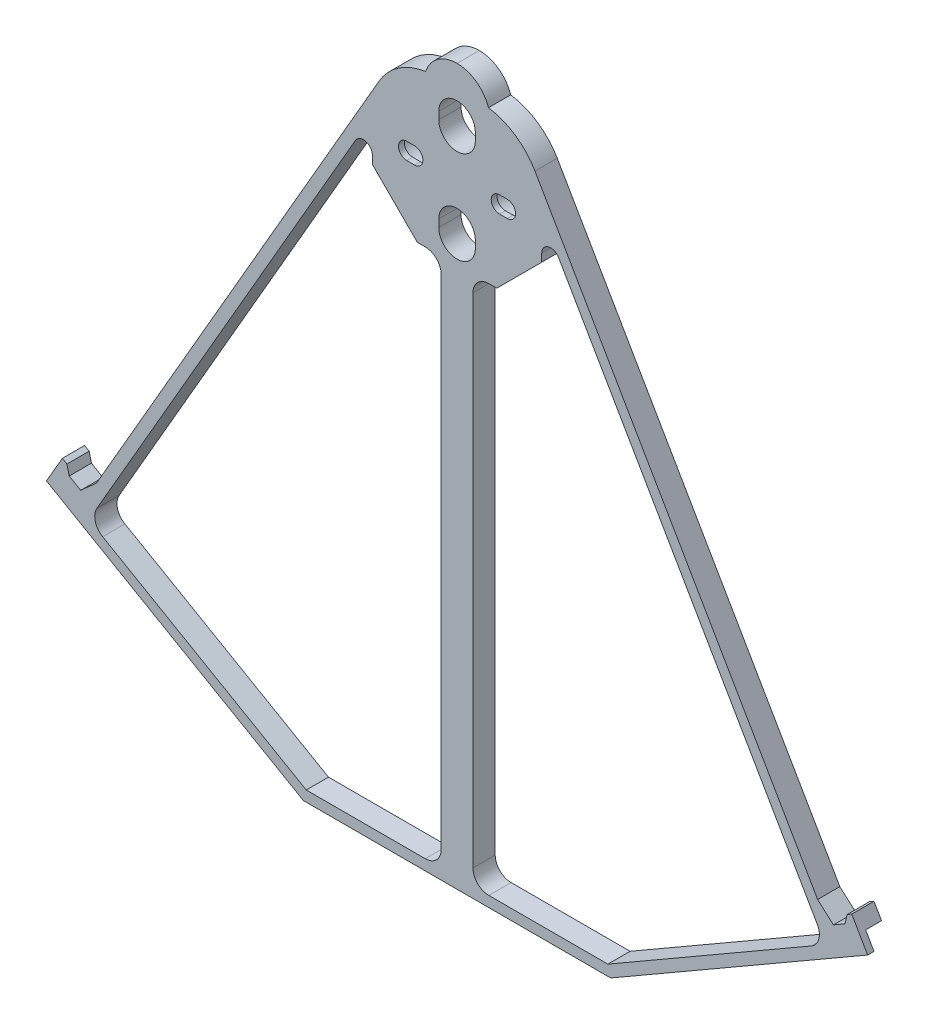
SolidWorks part; units mm, degrees
ref_plane "Alzado" through (0, 0, 0) normal (0, 0, 1) x (1, 0, 0)
ref_plane "Planta" through (0, 0, 0) normal (0, 1, 0) x (1, 0, 0)
ref_plane "Vista lateral" through (0, 0, 0) normal (1, 0, 0) x (0, 0, -1)
sketch "Croquis1" plane through (0, 0, 0) normal (0, 0, 1) x (1, 0, 0)
  line L0 (0, 0) -> (-29, 0)
  line L1 (0, 0) -> (0, 135)
  line L2 (-29, 0) -> (-77.4974, 28)
  line L3 (-77.4974, 28) -> (-74.4974, 33.1962)
  line L4 (-74.4974, 33.1962) -> (-73.6314, 32.6962)
  line L5 (-73.6314, 32.6962) -> (-74.2814, 31.5703)
  line L6 (-74.2814, 31.5703) -> (-69.9513, 29.0703)
  line L7 (-69.9513, 29.0703) -> (-8.7938, 134.9982)
  line L8 (-71.0381, 29.6978) -> (-68.0523, 32.3595)
  line L9 (-73.6314, 32.6962) -> (-73.2032, 30.9478)
  line L10 (0, 135) -> (-8.7938, 134.9982)
  point P4 (0, 0)
  dimension "D1" = 56
  dimension "D2" = 135
  dimension "D3" = 29
  dimension "D4" = 150
  dimension "D5" = 6
  dimension "D6" = 1
  dimension "D7" = 90
  dimension "D8" = 1.3
  dimension "D9" = 6
  dimension "D11" = 4
  dimension "D12" = 1.8
  dimension "D13" = 2.5
extrude "Saliente-Extruir1" add sketch "Croquis1" along normal blind 4.2 contours L1 L10 L7 L6 L5 L4 L3 L2 L0 | L8 L6 L7 | L9 L5 L6 region at (-25.21, 54.1538, 0) region at (-69.6806, 30.3759, 0) region at (-73.7053, 31.7381, 0)
sketch "Croquis2" plane through (0, 0, 4.2) normal (0, 0, 1) x (1, 0, 0)
  line L0 (0, 2) -> (-32.4641, 2)
  line L1 (0, 0) -> (0, 135) construction
  line L2 (-29, 0) -> (-77.4974, 28) construction
  line L3 (0, 0) -> (-29, 0) construction
  line L4 (-76.4974, 29.7321) -> (-28.4641, 2)
  line L5 (-68.0523, 32.3595) -> (-8.7938, 134.9982) construction
  line L6 (-70.4826, 23.95) -> (-6.3686, 134.9987)
  line L8 (-3, 2) -> (-3, 134.9994)
  line L10 (0, 135) -> (-8.7938, 134.9982) construction
  line L11 (0, 0) -> (0, 102) construction
  line L12 (0, 102) -> (0, 99) construction
  line L13 (0, 102) -> (-3, 102) construction
  line L14 (0, 99) -> (-3, 99) construction
  line L15 (-3, 102) -> (-7.5, 102)
  line L16 (-7.5, 102) -> (-15.9853, 110.4853)
  line L17 (-15.9853, 110.4853) -> (-15.9853, 111.9853)
  arc A2 (-3, 99) -> (-6, 102) centre (-6, 99) ccw
  circle A3 centre (-17.6886, 111.9853) radius 1.7033
  circle A4 centre (-65.3845, 26.7801) radius 3
  circle A5 centre (-6, 5) radius 3
  dimension "D7" = 4.5
  dimension "D8" = 3
  dimension "D12" = 6
  dimension "D13" = 6
  dimension "D1" = 2
  dimension "D2" = 2
  dimension "D3" = 2.1
  dimension "D4" = 3
  dimension "D5" = 102
  dimension "D6" = 3
  dimension "D9" = 12
  dimension "D10" = 1.5
  dimension "D11" = 45
extrude "Cortar-Extruir1" cut sketch "Croquis2" against normal blind 4.2 contours A3 L6 L4 L0 L8 A2 L15 L16 L17 | A3 | A4 | A5 region at (-26.8408, 48.996, 4.2) region at (-6, 5, 4.2) region at (-65.3845, 26.7801, 4.2) region at (-17.6886, 111.9853, 4.2)
sketch "Croquis3" plane through (0, 0, 4.2) normal (0, 0, 1) x (1, 0, 0)
  line L0 (0, 0) -> (0, 103) construction
  line L1 (0, 0) -> (0, 135) construction
  line L2 (0, 103) -> (0, 111.3) construction
  line L3 (-3.45, 106.45) -> (-3.45, 107.85)
  line L4 (3.45, 106.45) -> (3.45, 107.85)
  line L5 (0, 111.3) -> (0, 120.6) construction
  line L6 (0, 128.9) -> (0, 138.2) construction
  line L7 (0, 120.6) -> (0, 128.9) construction
  line L8 (3.45, 124.05) -> (3.45, 125.45)
  line L9 (-3.45, 124.05) -> (-3.45, 125.45)
  line L10 (0, 17.6) -> (0, 120.6) construction
  line L11 (0, 115.95) -> (-6.45, 115.95) construction
  line L12 (-6.45, 115.95) -> (-11.05, 115.95) construction
  line L13 (-9.475, 117.525) -> (-8.025, 117.525)
  line L14 (-8.025, 114.375) -> (-9.475, 114.375)
  circle A0 centre (0, 106.45) radius 3.45
  circle A1 centre (0, 107.85) radius 3.45
  circle A2 centre (0, 125.45) radius 3.45
  circle A3 centre (0, 124.05) radius 3.45
  circle A4 centre (-8.025, 115.95) radius 1.575
  circle A5 centre (-9.475, 115.95) radius 1.575
  line M28 (0, 0) -> (0, 135)
  dimension "D3" = 9.3
  dimension "D1" = 103
  dimension "D2" = 8.3
  dimension "D4" = 8.3
  dimension "D5" = 6.45
  dimension "D6" = 4.6
extrude "Cortar-Extruir2" cut sketch "Croquis3" against normal blind 4.2 contours A5 A4 L13 | A4 A5 | A5 A4 | A4 A5 | A5 L14 A4 | A3 A2 M28 | A2 A3 M28 | A3 A2 M28 | A3 A2 L9 | A0 A1 M28 | A1 A0 M28 | A1 A0 M28 | A1 L3 A0 region at (-1.7132, 122.0215, 4.2) region at (-3.4285, 107.15, 4.2) region at (-1.7132, 104.4215, 4.2) region at (-1.7132, 109.8785, 4.2) region at (-1.3783, 107.15, 4.2) region at (-3.4285, 124.75, 4.2) region at (-1.3783, 124.75, 4.2) region at (-1.7132, 127.4785, 4.2) region at (-10.0339, 115.95, 4.2) region at (-8.75, 117.4725, 4.2) region at (-7.4661, 115.95, 4.2) region at (-8.75, 114.4275, 4.2) region at (-8.75, 115.95, 4.2)
sketch "Croquis4" plane through (0, 0, 0) normal (0, 0, -1) x (-1, 0, 0)
  line L0 (8.75, 114.375) -> (8.75, 117.525) construction
  line L1 (8.025, 114.375) -> (9.475, 114.375) construction
  line L2 (9.475, 117.525) -> (8.025, 117.525) construction
  line L3 (6.45, 115.95) -> (11.05, 115.95) construction
  line L4 (4.6, 115.95) -> (12.9, 115.95) construction
  line L5 (8.05, 119.4) -> (9.45, 119.4)
  line L7 (8.05, 112.5) -> (9.45, 112.5)
  arc A1 (8.025, 117.525) -> (8.025, 114.375) centre (8.025, 115.95) ccw construction
  arc A2 (9.475, 114.375) -> (9.475, 117.525) centre (9.475, 115.95) ccw construction
  circle A3 centre (9.45, 115.95) radius 3.45
  circle A4 centre (8.05, 115.95) radius 3.45
  point P17 (8.75, 115.95)
  line M32 (8.025, 117.525) -> (9.475, 117.525)
  arc M33 (9.475, 117.525) -> (9.475, 114.375) centre (9.475, 115.95) cw
  line M34 (9.475, 114.375) -> (8.025, 114.375)
  arc M35 (8.025, 114.375) -> (8.025, 117.525) centre (8.025, 115.95) cw
  dimension "D1" = 8.3
extrude "Cortar-Extruir3" cut sketch "Croquis4" against normal blind 3.1 contours A3 A4 | A3 A4 M35 M32 M33 M34 | A4 A3 | A4 L7 A3 | A4 A3 L5 region at (-8.3936, 119.3019, 0) region at (-8.75, 119.3785, 0) region at (-11.8326, 118.3326, 0) region at (-8.75, 112.5215, 0) region at (-10.658, 118.073, 0)
sketch "Croquis5" plane through (0, 0, 0) normal (0, 0, -1) x (-1, 0, 0)
  line L0 (75.9224, 30.728) -> (71.2892, 28.053)
  line L1 (77.4974, 28) -> (74.4974, 33.1962) construction
  line L2 (71.2892, 28.053) -> (72.8642, 25.325)
  line L3 (29, 0) -> (77.4974, 28) construction
  dimension "D1" = 3.15
  dimension "D2" = 5.35
extrude "Cortar-Extruir4" cut sketch "Croquis5" against normal blind 3 and the other way through all
mirror "Simetría2" about plane through (0, 0, 4.2) normal (-1, 0, 0) of bodies 105
sketch "Croquis7" plane through (0, 0, 4.2) normal (0, 0, 1) x (1, 0, 0)
  line L0 (6.45, 115.95) -> (11.05, 115.95) construction
  line L1 (8.75, 114.375) -> (8.75, 117.525) construction
  line L2 (8.025, 114.375) -> (9.475, 114.375) construction
  line L3 (9.475, 117.525) -> (8.025, 117.525) construction
  line L4 (0, 120.6) -> (0, 128.9) construction
  line L5 (-3.45, 124.75) -> (3.45, 124.75) construction
  line L6 (-3.45, 124.05) -> (-3.45, 125.45) construction
  line L7 (3.45, 124.05) -> (3.45, 125.45) construction
  line L8 (8.75, 115.95) -> (0, 124.75) construction
  line L9 (0, 124.75) -> (-2.7575, 127.5233) construction
  line L10 (-2.7575, 127.5233) -> (-5.9304, 130.7143) construction
  line L11 (-11.05, 115.95) -> (-6.45, 115.95) construction
  line L12 (-8.75, 117.525) -> (-8.75, 114.375) construction
  line L13 (-9.475, 117.525) -> (-8.025, 117.525) construction
  line L14 (-8.025, 114.375) -> (-9.475, 114.375) construction
  line L15 (-8.75, 115.95) -> (0, 124.75) construction
  line L16 (0, 124.75) -> (2.7575, 127.5233) construction
  line L17 (2.7575, 127.5233) -> (5.9304, 130.7143) construction
  line L18 (3.45, 124.75) -> (14.7106, 124.75) construction
  line L19 (68.0523, 32.3595) -> (8.7938, 134.9982) construction
  line L20 (-3.45, 124.75) -> (-14.7106, 124.75) construction
  line L21 (-68.0523, 32.3595) -> (-8.7938, 134.9982) construction
  line L22 (-14.7106, 124.75) -> (-8.7938, 134.9982)
  line L23 (-8.7938, 134.9982) -> (0, 135)
  line L24 (8.7938, 134.9982) -> (14.7106, 124.75)
  line L25 (8.7938, 134.9982) -> (0, 135)
  arc A0 (8.025, 117.525) -> (8.025, 114.375) centre (8.025, 115.95) ccw construction
  arc A1 (9.475, 114.375) -> (9.475, 117.525) centre (9.475, 115.95) ccw construction
  arc A2 (-3.45, 124.05) -> (3.45, 124.05) centre (0, 124.05) ccw construction
  arc A3 (3.45, 125.45) -> (-3.45, 125.45) centre (0, 125.45) ccw construction
  arc A4 (-9.475, 117.525) -> (-9.475, 114.375) centre (-9.475, 115.95) ccw construction
  arc A5 (-8.025, 114.375) -> (-8.025, 117.525) centre (-8.025, 115.95) ccw construction
  circle A6 centre (0, 128.754) radius 6.246
  circle A7 centre (-4.1549, 118.6557) radius 12.1887
  circle A8 centre (4.1549, 118.6557) radius 12.1887
  dimension "D1" = 4.5
  dimension "D2" = 4.5
extrude "Cortar-Extruir5" cut sketch "Croquis7" against normal through all contours A7 A6 L23 L22 | A8 L24 L25 A6 region at (7.8971, 132.1703, 4.2) region at (-7.8971, 132.1703, 4.2)
